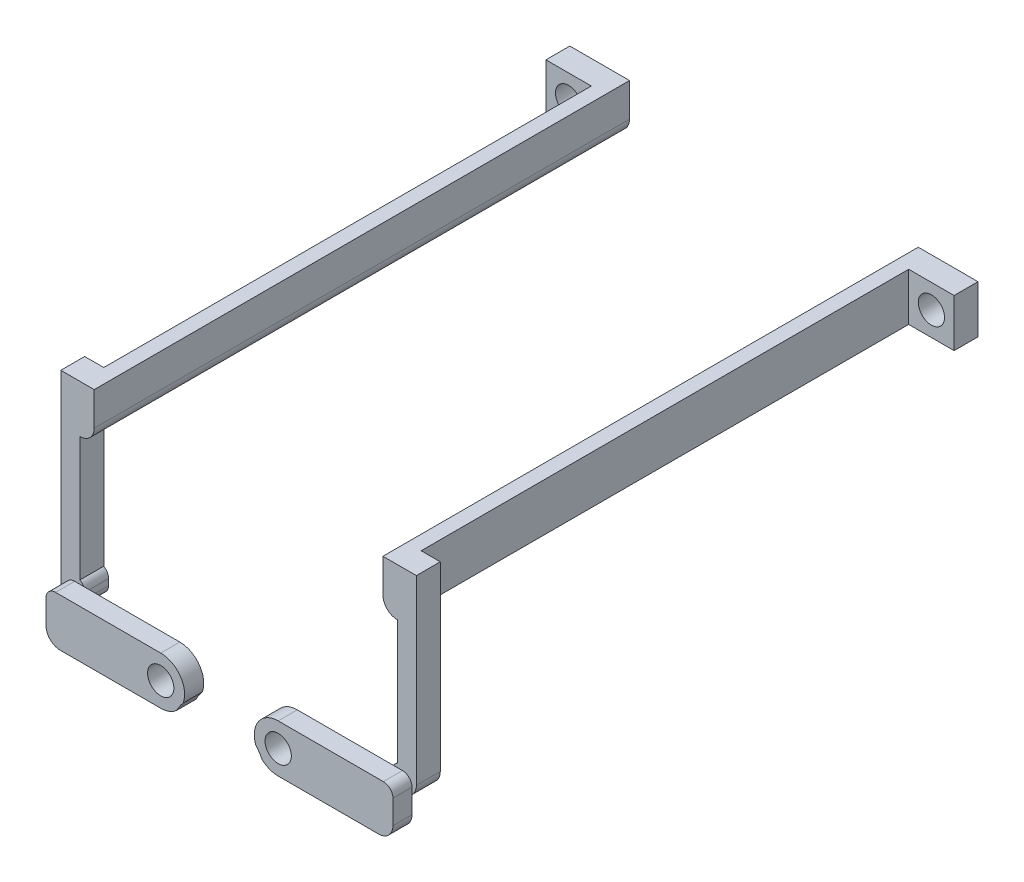
SolidWorks part; units mm, degrees
ref_plane "Front Plane" through (0, 0, 0) normal (0, 0, 1) x (1, 0, 0)
ref_plane "Top Plane" through (0, 0, 0) normal (0, 1, 0) x (1, 0, 0)
ref_plane "Right Plane" through (0, 0, 0) normal (1, 0, 0) x (0, 0, -1)
sketch "Sketch1" plane through (0, 0, 108) normal (0, 0, 1) x (1, 0, 0)
  line L9 (30.2, 50) -> (30.2, 43)
  line L10 (33.2, 40) -> (33.2, 14)
  line L11 (33.2, 14) -> (32.2, 14)
  line L12 (32.2, 14) -> (32.2, 9)
  line L13 (32.2, 9) -> (37.2, 9)
  line L14 (37.2, 9) -> (37.2, 40)
  line L15 (37.2, 40) -> (42.7, 40)
  line L16 (42.7, 40) -> (42.7, 50)
  line L17 (42.7, 50) -> (30.2, 50)
  line L18 (30.2, 50) -> (30.2, 43)
  line L19 (33.2, 40) -> (33.2, 14)
  line L20 (33.2, 14) -> (32.2, 14)
  line L21 (32.2, 14) -> (32.2, 9)
  line L22 (32.2, 9) -> (37.2, 9)
  line L23 (37.2, 9) -> (37.2, 40)
  line L24 (37.2, 40) -> (42.7, 40)
  line L25 (42.7, 40) -> (42.7, 50)
  line L26 (42.7, 50) -> (30.2, 50)
  line L27 (-37.2, 40) -> (-37.2, 9)
  line L28 (-37.2, 9) -> (-32.2, 9)
  line L29 (-32.2, 9) -> (-32.2, 14)
  line L30 (-32.2, 14) -> (-33.2, 14)
  line L31 (-33.2, 14) -> (-33.2, 40)
  line L32 (-30.2, 43) -> (-30.2, 50)
  line L33 (-30.2, 50) -> (-42.7, 50)
  line L34 (-42.7, 50) -> (-42.7, 40)
  line L35 (-42.7, 40) -> (-37.2, 40)
  line L36 (-37.2, 40) -> (-37.2, 9)
  line L37 (-37.2, 9) -> (-32.2, 9)
  line L38 (-32.2, 9) -> (-32.2, 14)
  line L39 (-32.2, 14) -> (-33.2, 14)
  line L40 (-33.2, 14) -> (-33.2, 40)
  line L41 (-30.2, 43) -> (-30.2, 50)
  line L42 (-30.2, 50) -> (-42.7, 50)
  line L43 (-42.7, 50) -> (-42.7, 40)
  line L44 (-42.7, 40) -> (-37.2, 40)
  circle A0 centre (-37.95, 45) radius 2.75 construction
  arc A1 (30.2, 43) -> (33.2, 40) centre (33.2, 43) ccw
  arc A2 (30.2, 43) -> (33.2, 40) centre (33.2, 43) ccw
  arc A3 (-33.2, 40) -> (-30.2, 43) centre (-33.2, 43) ccw
  arc A4 (-33.2, 40) -> (-30.2, 43) centre (-33.2, 43) ccw
  circle A5 centre (37.95, 45) radius 2.75 construction
  circle A6 centre (-37.95, 45) radius 2.75
  circle A7 centre (37.95, 45) radius 2.75
  dimension "D1" = 0
  dimension "D2" = 0
extrude "Boss-Extrude1" add sketch "Sketch1" along normal blind 5
sketch "Sketch2" plane through (0, 0, 220) normal (0, 0, 1) x (1, 0, 0)
  line L9 (42.7, 50) -> (30.2, 50)
  line L10 (30.2, 50) -> (30.2, 43)
  line L11 (33.2, 40) -> (33.2, 14)
  line L12 (33.2, 14) -> (32.2, 14)
  line L13 (32.2, 14) -> (32.2, 9)
  line L14 (32.2, 9) -> (37.2, 9)
  line L15 (37.2, 9) -> (37.2, 40)
  line L16 (37.2, 40) -> (42.7, 40)
  line L17 (42.7, 40) -> (42.7, 50)
  line L18 (42.7, 50) -> (30.2, 50)
  line L19 (30.2, 50) -> (30.2, 43)
  line L20 (33.2, 40) -> (33.2, 14)
  line L21 (33.2, 14) -> (32.2, 14)
  line L22 (32.2, 14) -> (32.2, 9)
  line L23 (32.2, 9) -> (37.2, 9)
  line L24 (37.2, 9) -> (37.2, 40)
  line L25 (37.2, 40) -> (42.7, 40)
  line L26 (42.7, 40) -> (42.7, 50)
  line L27 (-42.7, 40) -> (-37.2, 40)
  line L28 (-37.2, 40) -> (-37.2, 9)
  line L29 (-37.2, 9) -> (-32.2, 9)
  line L30 (-32.2, 9) -> (-32.2, 14)
  line L31 (-32.2, 14) -> (-33.2, 14)
  line L32 (-33.2, 14) -> (-33.2, 40)
  line L33 (-30.2, 43) -> (-30.2, 50)
  line L34 (-30.2, 50) -> (-42.7, 50)
  line L35 (-42.7, 50) -> (-42.7, 40)
  line L36 (-42.7, 40) -> (-37.2, 40)
  line L37 (-37.2, 40) -> (-37.2, 9)
  line L38 (-37.2, 9) -> (-32.2, 9)
  line L39 (-32.2, 9) -> (-32.2, 14)
  line L40 (-32.2, 14) -> (-33.2, 14)
  line L41 (-33.2, 14) -> (-33.2, 40)
  line L42 (-30.2, 43) -> (-30.2, 50)
  line L43 (-30.2, 50) -> (-42.7, 50)
  line L44 (-42.7, 50) -> (-42.7, 40)
  arc A1 (30.2, 43) -> (33.2, 40) centre (33.2, 43) ccw
  arc A2 (30.2, 43) -> (33.2, 40) centre (33.2, 43) ccw
  arc A3 (-33.2, 40) -> (-30.2, 43) centre (-33.2, 43) ccw
  arc A4 (-33.2, 40) -> (-30.2, 43) centre (-33.2, 43) ccw
  dimension "D1" = 0
  dimension "D2" = 0
extrude "Boss-Extrude2" add sketch "Sketch2" against normal blind 5 separate body
sketch "Sketch3" plane through (0, 0, 113) normal (0, 0, 1) x (1, 0, 0)
  line L0 (33.2, 40) -> (33.2, 50)
  line L1 (42.7, 50) -> (30.2, 50) construction
  line L2 (-33.2, 40) -> (-33.2, 50)
  line L3 (-30.2, 50) -> (-42.7, 50) construction
  line L13 (-42.7, 40) -> (-37.2, 40)
  line L14 (-37.2, 40) -> (-37.2, 9)
  line L15 (-37.2, 9) -> (-32.2, 9)
  line L16 (-32.2, 9) -> (-32.2, 14)
  line L17 (-32.2, 14) -> (-33.2, 14)
  line L18 (-33.2, 14) -> (-33.2, 40)
  line L19 (-30.2, 43) -> (-30.2, 50)
  line L20 (-30.2, 50) -> (-42.7, 50)
  line L21 (-42.7, 50) -> (-42.7, 40)
  line L22 (-42.7, 40) -> (-37.2, 40)
  line L23 (-37.2, 40) -> (-37.2, 9)
  line L24 (-37.2, 9) -> (-32.2, 9)
  line L25 (-32.2, 9) -> (-32.2, 14)
  line L26 (-32.2, 14) -> (-33.2, 14)
  line L27 (-33.2, 14) -> (-33.2, 40)
  line L28 (-30.2, 43) -> (-30.2, 50)
  line L29 (-30.2, 50) -> (-42.7, 50)
  line L30 (-42.7, 50) -> (-42.7, 40)
  line L31 (42.7, 50) -> (30.2, 50)
  line L32 (30.2, 50) -> (30.2, 43)
  line L33 (33.2, 40) -> (33.2, 14)
  line L34 (33.2, 14) -> (32.2, 14)
  line L35 (32.2, 14) -> (32.2, 9)
  line L36 (32.2, 9) -> (37.2, 9)
  line L37 (37.2, 9) -> (37.2, 40)
  line L38 (37.2, 40) -> (42.7, 40)
  line L39 (42.7, 40) -> (42.7, 50)
  line L40 (42.7, 50) -> (30.2, 50)
  line L41 (30.2, 50) -> (30.2, 43)
  line L42 (33.2, 40) -> (33.2, 14)
  line L43 (33.2, 14) -> (32.2, 14)
  line L44 (32.2, 14) -> (32.2, 9)
  line L45 (32.2, 9) -> (37.2, 9)
  line L46 (37.2, 9) -> (37.2, 40)
  line L47 (37.2, 40) -> (42.7, 40)
  line L48 (42.7, 40) -> (42.7, 50)
  arc A1 (-33.2, 40) -> (-30.2, 43) centre (-33.2, 43) ccw
  arc A2 (-33.2, 40) -> (-30.2, 43) centre (-33.2, 43) ccw
  arc A3 (30.2, 43) -> (33.2, 40) centre (33.2, 43) ccw
  arc A4 (30.2, 43) -> (33.2, 40) centre (33.2, 43) ccw
  line M21 (42.7, 50) -> (30.2, 50)
  line M22 (30.2, 50) -> (30.2, 43)
  arc M23 (30.2, 43) -> (33.2, 40) centre (33.2, 43) ccw
  dimension "D1" = 0
  dimension "D2" = 0
extrude "Boss-Extrude3" add sketch "Sketch3" along normal up to surface (102 mm away) contours L0 M23 M21 M22 | L2 A2 L28 L29 region at (31.7571, 45.2979, 113) region at (-31.7571, 45.2979, 113) up to face at (-35.0379, 30.8379, 215)
sketch "Sketch4" plane through (0, 0, 220) normal (0, 0, 1) x (1, 0, 0)
  line L1 (-42.7, 50) -> (-37.2, 50)
  line L2 (-42.7, 50) -> (-42.7, 40)
  line L3 (-42.7, 40) -> (-37.2, 40)
  line L4 (-37.2, 50) -> (-37.2, 40)
  line L5 (37.2, 40) -> (42.7, 40)
  line L6 (37.2, 40) -> (37.2, 50)
  line L7 (37.2, 50) -> (42.7, 50)
  line L8 (42.7, 40) -> (42.7, 50)
extrude "Cut-Extrude1" cut sketch "Sketch4" against normal up to surface (5 mm away) up to face at (-35.9778, 29.5556, 215)
sketch "Sketch5" plane through (0, 0, 220) normal (0, 0, 1) x (1, 0, 0)
  line L0 (12.2887, 13.2177) -> (36.2887, 13.2177)
  line L1 (12.2887, 3.2177) -> (36.2887, 3.2177)
  line L2 (36.2887, 3.2177) -> (36.2887, 13.2177)
  line L3 (-12.2887, 3.2177) -> (-38.1106, 3.2177)
  line L4 (-12.2887, 13.2177) -> (-36.2887, 13.2177)
  line L5 (-36.2887, 13.2177) -> (-36.2887, 0)
  circle A0 centre (-12.2887, 8.2177) radius 2.75 construction
  circle A1 centre (-12.2887, 8.2177) radius 2.75
  circle A2 centre (12.2887, 8.2177) radius 2.75 construction
  circle A3 centre (12.2887, 8.2177) radius 2.75
  circle A4 centre (-12.2887, 8.2177) radius 5
  circle A5 centre (12.2887, 8.2177) radius 5
  circle M4 centre (12.2887, 8.2177) radius 2.75
  line M7 (-20.7532, 14.75) -> (-12.7605, -5.1303)
  line M19 (12.7605, -5.1303) -> (20.7532, 14.75)
  circle M27 centre (0, 0) radius 10
  circle M28 centre (-12.2887, 8.2177) radius 2.75
  dimension "D1" = 10
  dimension "D2" = 10
  dimension "D3" = 24
  dimension "D4" = 24
extrude "Boss-Extrude4" add sketch "Sketch5" along normal blind 4 contours A4 M27 M28 | L4 L5 L3 M7 | A4 L4 L3 M7 | L1 L2 L0 M19 | A5 L1 L0 M19 | A5 M27 M4 region at (17.1979, 9.9707, 220) region at (15.7243, 11.6532, 220) region at (27.1707, 8.0332, 220) region at (-8.4302, 5.6374, 220) region at (-17.1979, 9.9707, 220) region at (-27.1707, 8.0332, 220)
fillet "Fillet1" radius 3 2 edges at (-36.2887, 3.2177, 222) (-37.2, 9, 217.5)
fillet "Fillet2" radius 3 2 edges at (37.2, 9, 217.5) (36.2887, 3.2177, 222)
fillet "Fillet3" radius 2 1 edges at (36.2887, 13.2177, 222)
fillet "Fillet4" radius 2 1 edges at (-36.2887, 13.2177, 222)
fillet "Fillet5" radius 2 1 edges at (-32.2, 14, 217.5)
fillet "Fillet6" radius 2 1 edges at (32.2, 14, 217.5)
fillet "Fillet7" radius 2 1 edges at (32.2, 9, 217.5)
fillet "Fillet8" radius 2 1 edges at (-32.2, 9, 217.5)
sketch "Sketch7" plane through (0, 0, 113) normal (0, 0, 1) x (1, 0, 0)
  line L0 (-33.2, 40) -> (-37.2, 40)
  line L1 (37.2, 40) -> (33.2, 40)
  line L9 (-33.2, 14) -> (-33.2, 40)
  line L10 (-33.2, 40) -> (-33.2, 50)
  line L11 (-33.2, 50) -> (-42.7, 50)
  line L12 (-42.7, 50) -> (-42.7, 40)
  line L13 (-42.7, 40) -> (-37.2, 40)
  line L14 (-37.2, 40) -> (-37.2, 9)
  line L15 (-37.2, 9) -> (-32.2, 9)
  line L16 (-32.2, 9) -> (-32.2, 14)
  line L17 (-32.2, 14) -> (-33.2, 14)
  line L18 (-33.2, 14) -> (-33.2, 40)
  line L19 (-33.2, 40) -> (-33.2, 50)
  line L20 (-33.2, 50) -> (-42.7, 50)
  line L21 (-42.7, 50) -> (-42.7, 40)
  line L22 (-42.7, 40) -> (-37.2, 40)
  line L23 (-37.2, 40) -> (-37.2, 9)
  line L24 (-37.2, 9) -> (-32.2, 9)
  line L25 (-32.2, 9) -> (-32.2, 14)
  line L26 (-32.2, 14) -> (-33.2, 14)
  line L27 (33.2, 50) -> (33.2, 40)
  line L28 (33.2, 40) -> (33.2, 14)
  line L29 (33.2, 14) -> (32.2, 14)
  line L30 (32.2, 14) -> (32.2, 9)
  line L31 (32.2, 9) -> (37.2, 9)
  line L32 (37.2, 9) -> (37.2, 40)
  line L33 (37.2, 40) -> (42.7, 40)
  line L34 (42.7, 40) -> (42.7, 50)
  line L35 (42.7, 50) -> (33.2, 50)
  line L36 (33.2, 50) -> (33.2, 40)
  line L37 (33.2, 40) -> (33.2, 14)
  line L38 (33.2, 14) -> (32.2, 14)
  line L39 (32.2, 14) -> (32.2, 9)
  line L40 (32.2, 9) -> (37.2, 9)
  line L41 (37.2, 9) -> (37.2, 40)
  line L42 (37.2, 40) -> (42.7, 40)
  line L43 (42.7, 40) -> (42.7, 50)
  line L44 (42.7, 50) -> (33.2, 50)
  line M20 (-33.2, 14) -> (-33.2, 40)
  line M25 (-37.2, 40) -> (-37.2, 9)
  line M26 (-37.2, 9) -> (-32.2, 9)
  line M27 (-32.2, 9) -> (-32.2, 14)
  line M28 (-32.2, 14) -> (-33.2, 14)
  dimension "D1" = 0
  dimension "D2" = 0
extrude "Cut-Extrude2" cut sketch "Sketch7" against normal up to surface (5 mm away) contours L0 M20 M25 M26 M27 M28 | L40 L41 L1 L37 L38 L39 region at (-35.1031, 23.9961, 113) region at (35.1031, 23.9961, 113) up to face at (-35.0379, 30.8379, 108)
